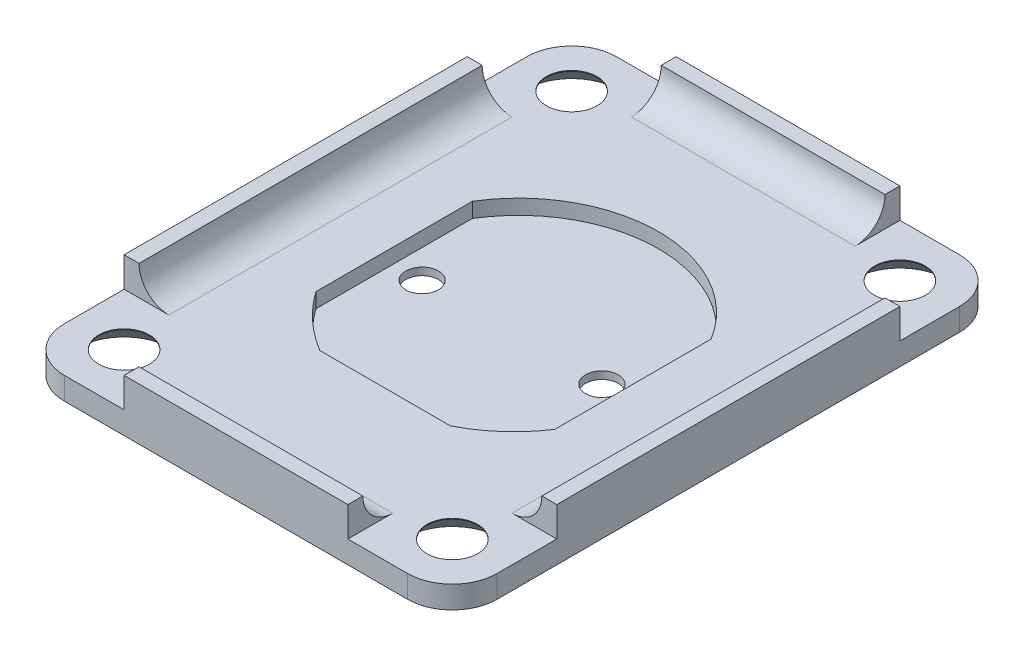
SolidWorks part; units mm, degrees
material "ABS"
ref_plane "Front Plane" through (0, 0, 0) normal (0, 0, 1) x (1, 0, 0)
ref_plane "Top Plane" through (0, 0, 0) normal (0, 1, 0) x (1, 0, 0)
ref_plane "Right Plane" through (0, 0, 0) normal (1, 0, 0) x (0, 0, -1)
sketch "Sketch5" plane through (0, 0, 0) normal (0, 1, 0) x (1, 0, 0)
  line L1 (14.5, -18.5) -> (-14.5, -18.5)
  line L2 (14.5, -18.5) -> (14.5, 18.5)
  line L3 (14.5, 18.5) -> (-14.5, 18.5)
  line L4 (-14.5, -18.5) -> (-14.5, 18.5)
  line L5 (14.5, -18.5) -> (-14.5, 18.5) construction
  line L6 (14.5, 18.5) -> (-14.5, -18.5) construction
  point P0 (0, 0)
  dimension "D1" = 37
  dimension "D2" = 29
extrude "Boss-Extrude3" add sketch "Sketch5" along normal blind 0.5
sketch "Sketch6" plane through (0, 0.5, 0) normal (0, 1, 0) x (1, 0, 0)
  line L0 (0, 0) -> (0, 5.1824) construction
  circle A0 centre (-6.025, 0) radius 1.095
  circle A1 centre (6.025, 0) radius 1.095
  dimension "D2" = 2.19
  dimension "D1" = 12.05
extrude "Cut-Extrude1" cut sketch "Sketch6" against normal through all both and the other way through all
sketch "Sketch7" plane through (0, 0.5, 0) normal (0, 1, 0) x (1, 0, 0)
  line L5 (8.0658, -5.2018) -> (8.0658, 5.2809)
  line L6 (-7.9342, -5.2115) -> (-7.9342, 5.2809)
  line L7 (4.3629, -8.4965) -> (-4.3854, -8.4965)
  line L9 (-14.5, -18.5) -> (14.5, -18.5)
  line L10 (-14.5, -18.5) -> (-14.5, 18.5)
  line L11 (-14.5, 18.5) -> (14.5, 18.5)
  line L12 (14.5, -18.5) -> (14.5, 18.5)
  line L13 (-14.5, 18.5) -> (-14.5, -18.5) construction
  line L15 (-14.5, -18.5) -> (14.5, -18.5) construction
  arc A3 (-7.9342, 5.2809) -> (8.0658, 5.2809) centre (0.0658, 0.3732) cw
  arc A4 (-7.9342, -5.2115) -> (-4.3854, -8.4965) centre (1.7365, 1.6768) ccw
  arc A5 (4.3629, -8.4965) -> (8.0658, -5.2018) centre (0.0516, 0.077) ccw
  point P6 (0, 0)
  line M18 (-14.5, 18.5) -> (-14.5, -18.5)
  line M19 (-14.5, -18.5) -> (14.5, -18.5)
  line M20 (14.5, -18.5) -> (14.5, 18.5)
  line M21 (14.5, 18.5) -> (-14.5, 18.5)
extrude "Boss-Extrude4" add sketch "Sketch7" along normal blind 1 contours A5 L7 A4 L6 A3 L5 M21 M18 M19 M20 region at (-14.0299, 0.5, 0)
sketch "Sketch8" plane through (0, 1.5, 0) normal (0, 1, 0) x (1, 0, 0)
  line L1 (-14.5, -18.5) -> (-7.5, -18.5)
  line L2 (-14.5, -18.5) -> (-14.5, -11.5)
  line L3 (-14.5, -11.5) -> (-7.5, -11.5)
  line L4 (-7.5, -18.5) -> (-7.5, -11.5)
  line L5 (14.5, -18.5) -> (7.5, -18.5)
  line L6 (14.5, -18.5) -> (14.5, -11.5)
  line L7 (14.5, -11.5) -> (7.5, -11.5)
  line L8 (7.5, -18.5) -> (7.5, -11.5)
  line L9 (14.5, 18.5) -> (7.5, 18.5)
  line L10 (14.5, 18.5) -> (14.5, 11.5)
  line L11 (14.5, 11.5) -> (7.5, 11.5)
  line L12 (7.5, 18.5) -> (7.5, 11.5)
  line L13 (-14.5, 18.5) -> (-7.5, 18.5)
  line L14 (-14.5, 18.5) -> (-14.5, 11.5)
  line L15 (-14.5, 11.5) -> (-7.5, 11.5)
  line L16 (-7.5, 18.5) -> (-7.5, 11.5)
  line L17 (-7.5, -18.5) -> (7.5, -18.5)
  line L18 (-7.5, -18.5) -> (-7.5, -17.5)
  line L19 (-7.5, -17.5) -> (7.5, -17.5)
  line L20 (7.5, -18.5) -> (7.5, -17.5)
  line L21 (-14.5, -11.5) -> (-13.5, -11.5)
  line L22 (-14.5, -11.5) -> (-14.5, 11.5)
  line L23 (-14.5, 11.5) -> (-13.5, 11.5)
  line L24 (-13.5, -11.5) -> (-13.5, 11.5)
  line L25 (-7.5, 18.5) -> (7.5, 18.5)
  line L26 (-7.5, 18.5) -> (-7.5, 17.5)
  line L27 (-7.5, 17.5) -> (7.5, 17.5)
  line L28 (7.5, 18.5) -> (7.5, 17.5)
  line L29 (14.5, 11.5) -> (13.5, 11.5)
  line L30 (14.5, 11.5) -> (14.5, -11.5)
  line L31 (14.5, -11.5) -> (13.5, -11.5)
  line L32 (13.5, 11.5) -> (13.5, -11.5)
  line M23 (14.5, 18.5) -> (-14.5, 18.5)
  line M24 (-14.5, 18.5) -> (-14.5, -18.5)
  line M25 (-14.5, -18.5) -> (14.5, -18.5)
  line M26 (14.5, -18.5) -> (14.5, 18.5)
  dimension "D1" = 7
  dimension "D2" = 7
  dimension "D3" = 7
  dimension "D4" = 7
  dimension "D5" = 7
  dimension "D6" = 7
  dimension "D7" = 7
  dimension "D8" = 7
  dimension "D9" = 1
  dimension "D10" = 1
  dimension "D11" = 1
  dimension "D12" = 1
extrude "Boss-Extrude5" add sketch "Sketch8" along normal blind 2 contours L19 L4 L8 M25 | L3 L24 L15 M24 | L16 L27 L12 M23 | L11 L32 L7 M26 region at (0, 1.5, 18) region at (-14, 1.5, 0) region at (14, 1.5, 0) region at (0, 1.5, -18)
fillet "Fillet1" radius 3 4 edges at (-14.5, 0.75, -18.5) (14.5, 0.75, -18.5) (-14.5, 0.75, 18.5) (14.5, 0.75, 18.5)
sketch "Sketch10" plane through (0, 0, 0) normal (0, -1, 0) x (1, 0, 0)
  line L1 (11, 15) -> (-11, 15) construction
  line L2 (11, 15) -> (11, -15) construction
  line L3 (11, -15) -> (-11, -15) construction
  line L4 (-11, 15) -> (-11, -15) construction
  line L5 (11, 15) -> (-11, -15) construction
  line L6 (11, -15) -> (-11, 15) construction
  point P0 (0, 0)
  dimension "D1" = 22
  dimension "D2" = 30
hole_wizard "CSK for M3 Countersunk Flat Head Screw1" positions "3DSketch1" profile "Sketch11" countersink size "M3" standard "ISO" end condition up to next
sketch3d "3DSketch1"
  point P0 (-11, 0, -15)
  point P3 (11, 0, -15)
  point P6 (11, 0, 15)
  point P9 (-11, 0, 15)
sketch "Sketch11" plane through (-11, 0, -15) normal (1, 0, 0) x (0, 0, -1)
  line L0 (0, 0) -> (0, 1.5)
  line L1 (0, 1.5) -> (1.7, 1.5)
  line L2 (1.7, 1.5) -> (1.7, 1.45)
  line L3 (1.7, 1.45) -> (3.15, 0)
  line L5 (3.15, 0) -> (0, 0)
  line L6 (-1.7, 1.45) -> (-3.15, 0) construction
  line L11 (0, -6.35) -> (0, 107.95) construction
  dimension "Thru Hole Dia." = 3.4
  dimension "Thru Hole Depth" = 1.5
  dimension "Near C'Sink Dia." = 6.3
  dimension "Near C'Sink Angle" = 90
ref_axis "Axis1" through (0, 1.575, 0) along (0, -1, 0)
fillet "Fillet2" radius 2 4 edges at (-13.5, 1.5, 0) (13.5, 1.5, 0) (0, 1.5, -17.5) (0, 1.5, 17.5)
